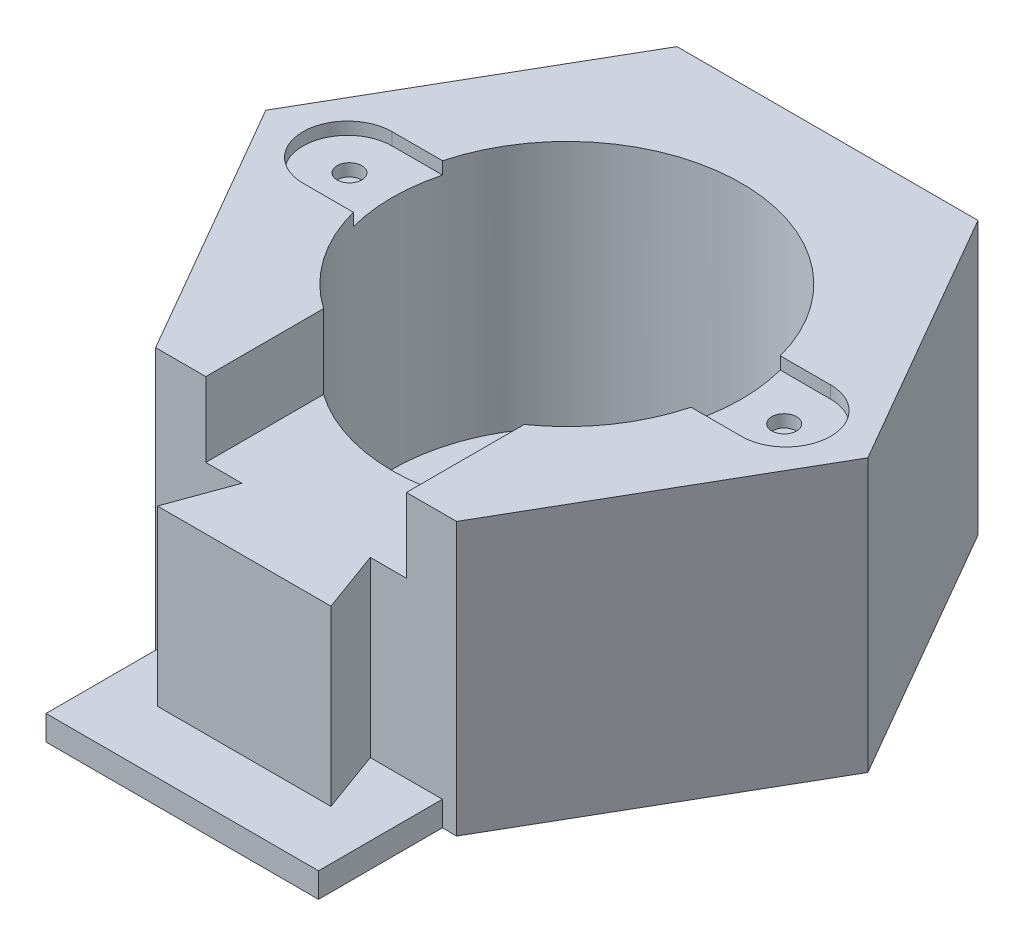
SolidWorks part; units mm, degrees
ref_plane "Front Plane" through (0, 0, 0) normal (0, 0, 1) x (1, 0, 0)
ref_plane "Top Plane" through (0, 0, 0) normal (0, 1, 0) x (1, 0, 0)
ref_plane "Right Plane" through (0, 0, 0) normal (1, 0, 0) x (0, 0, -1)
sketch "Sketch1" plane through (0, 0, 0) normal (0, 1, 0) x (1, 0, 0)
  line L0 (-33.6669, 0) -> (32.8036, 0) construction
  line L1 (0, 37.5104) -> (0, -35.9484) construction
  line L2 (-17.7, 3.6) -> (-13.6327, 3.6)
  line L3 (-17.7, -3.6) -> (-13.6327, -3.6)
  line L4 (13.6327, 3.6) -> (17.7, 3.6)
  line L5 (24.3, 0) -> (12.15, 21.0444)
  line L6 (12.15, 21.0444) -> (-12.15, 21.0444)
  line L7 (-12.15, 21.0444) -> (-24.3, 0)
  line L8 (-24.3, 0) -> (-12.15, -21.0444)
  line L9 (-12.15, -21.0444) -> (12.15, -21.0444)
  line L10 (12.15, -21.0444) -> (24.3, 0)
  line L12 (-8.1, -11.5412) -> (-8.1, -31.0444)
  line L13 (-8.1, -31.0444) -> (8.1, -31.0444)
  line L14 (8.1, -11.5412) -> (8.1, -31.0444)
  line L15 (-11, -21.0444) -> (11, -21.0444)
  line L16 (-11, -21.0444) -> (-11, -31.0444)
  line L17 (-11, -31.0444) -> (11, -31.0444)
  line L18 (11, -21.0444) -> (11, -31.0444)
  line L19 (13.6327, -3.6) -> (17.7, -3.6)
  line L20 (-8.1, -17.2) -> (8.1, -17.2)
  line L21 (-5.1807, -21.0444) -> (-7.0005, -26.0444)
  line L22 (-7.0005, -26.0444) -> (7.0005, -26.0444)
  line L23 (7.0005, -26.0444) -> (5.1807, -21.0444)
  circle A0 centre (0, 0) radius 14.1
  arc A1 (17.7, -3.6) -> (17.7, 3.6) centre (17.7, 0) ccw
  arc A2 (-17.7, -3.6) -> (-17.7, 3.6) centre (-17.7, 0) cw
  circle A5 centre (0, 0) radius 21.0444 construction
  circle A6 centre (17.55, 0) radius 1
  circle A7 centre (-17.55, 0) radius 1
  point P42 (0, 0)
  dimension "D1" = 28.2
  dimension "D2" = 7.2
  dimension "D3" = 2
  dimension "D5" = 3
  dimension "D4" = 35.4
  dimension "D6" = 16.2
  dimension "D7" = 10
  dimension "D8" = 22
  dimension "D9" = 35.1
  dimension "D10" = 17.2
  dimension "D11" = 5
  dimension "D12" = 70
  dimension "D13" = 14.001
  dimension "D14" = 70
extrude "Boss-Extrude5" add sketch "Sketch1" along normal blind 20 contours A7 | A6 region at (17.55, 0, 0) region at (-17.55, 0, 0)
extrude "Boss-Extrude6" add sketch "Sketch1<3>" along normal blind 2 separate body contours A0 region at (0, 0, 0)
sketch "Sketch1<3>" plane through (0, 0, 0) normal (0, 1, 0) x (1, 0, 0) same geometry as "Sketch1"
extrude "Boss-Extrude7" add sketch "Sketch1<4>" along normal blind 21 contours A2 L3 A0 L2 A7 | L19 A1 L4 A0 A6 region at (-15.6663, 0, -3.4948) region at (15.6663, 0, -3.4948)
sketch "Sketch1<4>" plane through (0, 0, 0) normal (0, 1, 0) x (1, 0, 0) same geometry as "Sketch1"
extrude "Boss-Extrude8" add sketch "Sketch1<5>" along normal blind 22 contours L3 A2 L2 A0 L4 A1 L19 L14 L9 L10 L5 L6 L7 L8 L12 region at (-21.9429, 0, 0)
sketch "Sketch1<5>" plane through (0, 0, 0) normal (0, 1, 0) x (1, 0, 0) same geometry as "Sketch1"
extrude "Boss-Extrude9" add sketch "Sketch1<7>" along normal blind 2 contours L23 L22 L21 L9 L12 L13 L14 | L18 L9 L14 L17 | L16 L17 L12 L9 region at (-9.55, 0, 26.0444) region at (0, 0, 27.4756) region at (9.55, 0, 26.0444)
sketch "Sketch1<7>" plane through (0, 0, 0) normal (0, 1, 0) x (1, 0, 0) same geometry as "Sketch1"
extrude "Boss-Extrude10" add sketch "Sketch1<8>" along normal blind 16 contours A0 L12 L20 L14 | L20 L12 L9 L15 L14 | L22 L23 L15 L21 region at (0, 0, 15.1683) region at (0, 0, 19.1222) region at (0, 0, 23.6689)
sketch "Sketch1<8>" plane through (0, 0, 0) normal (0, 1, 0) x (1, 0, 0) same geometry as "Sketch1"
